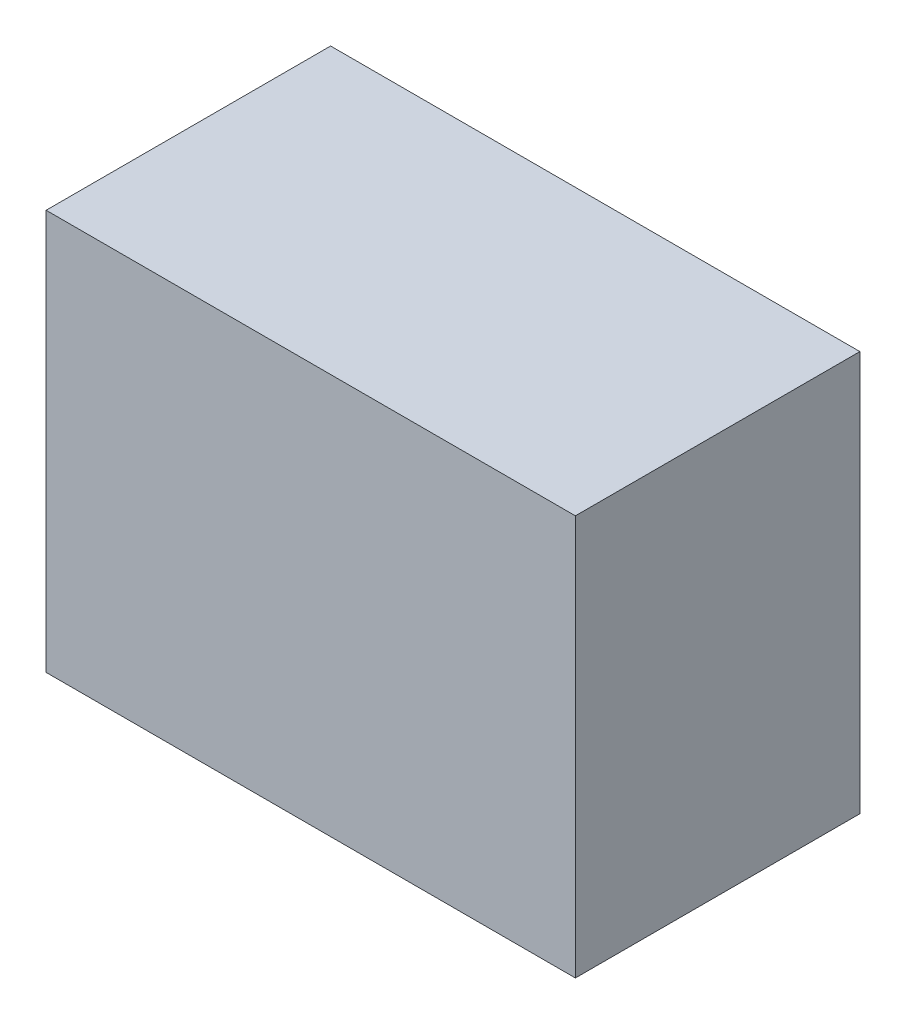
SolidWorks part; units mm, degrees
ref_plane "Front Plane" through (0, 0, 0) normal (0, 0, 1) x (1, 0, 0)
ref_plane "Top Plane" through (0, 0, 0) normal (0, 1, 0) x (1, 0, 0)
ref_plane "Right Plane" through (0, 0, 0) normal (1, 0, 0) x (0, 0, -1)
sketch "Sketch2" plane through (0, 0, 0) normal (0, 1, 0) x (1, 0, 0)
  line L1 (-160, -86) -> (160, -86)
  line L2 (-160, -86) -> (-160, 86)
  line L3 (-160, 86) -> (160, 86)
  line L4 (160, -86) -> (160, 86)
  line L5 (-160, -86) -> (160, 86) construction
  line L6 (-160, 86) -> (160, -86) construction
  point P0 (0, 0)
  dimension "D1" = 320
  dimension "D2" = 172
extrude "Boss-Extrude1" add sketch "Sketch2" along normal blind 242
equation "\"PCWidth\"= 172mm"
equation "\"PCLength\"= 320mm"
equation "\"PCHeight\"= 242mm"
equation "\"WallThickness\"= 10mm"
equation "\"ThermoBarrierThickness\"= 3mm"
equation "\"HotSideGap\"= 50mm"
equation "\"D1@Boss-Extrude1\"=\"PCHeight\""
equation "\"D1@Sketch2\"=\"PCLength\""
equation "\"D2@Sketch2\"=\"PCWidth\""
